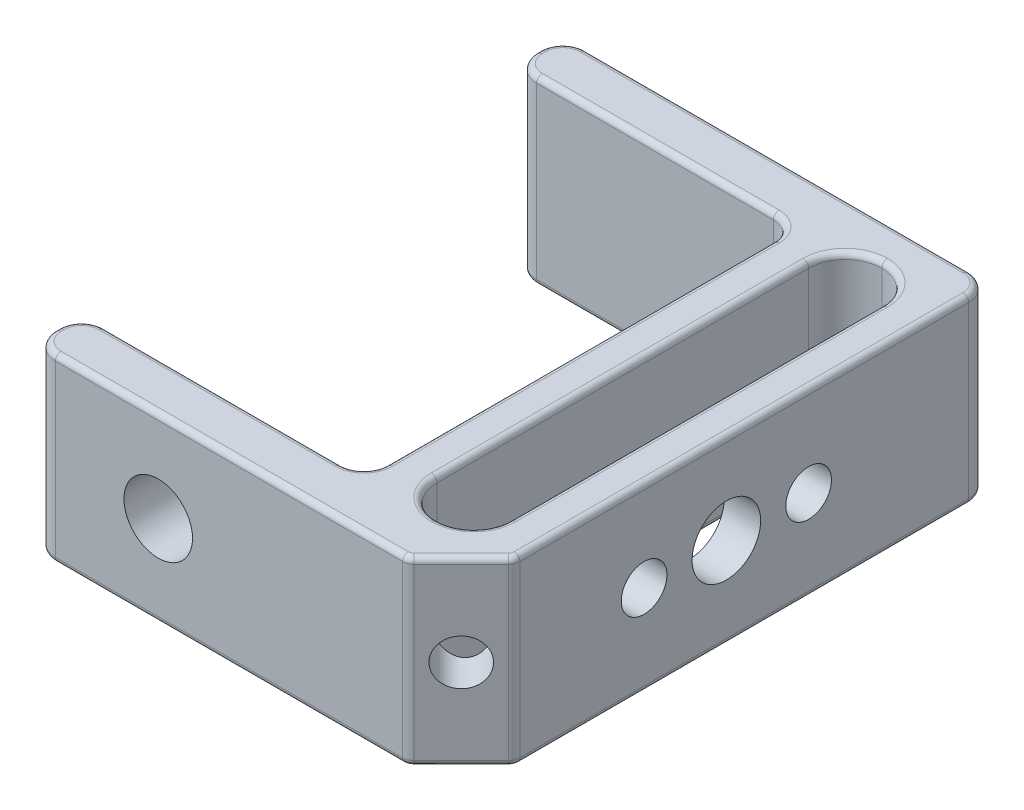
SolidWorks part; units mm, degrees
material "BUTYL"
ref_plane "Front Plane" through (0, 0, 0) normal (0, 0, 1) x (1, 0, 0)
ref_plane "Top Plane" through (0, 0, 0) normal (0, 1, 0) x (1, 0, 0)
ref_plane "Right Plane" through (0, 0, 0) normal (1, 0, 0) x (0, 0, -1)
sketch "Sketch1" plane through (0, 0, 0) normal (0, 1, 0) x (1, 0, 0)
  line L0 (0, 0) -> (0, -6.7945)
  line L1 (0, -6.7945) -> (39.243, -6.7945)
  line L2 (39.243, -6.7945) -> (39.243, -66.8655)
  line L3 (39.243, -66.8655) -> (0, -66.8655)
  line L4 (0, -66.8655) -> (0, -73.66)
  line L5 (0, 0) -> (59.563, 0)
  line L6 (59.563, 0) -> (59.563, -66.167)
  line L7 (59.563, -66.167) -> (52.07, -73.66)
  line L8 (52.07, -73.66) -> (0, -73.66)
  line L9 (44.323, -5.08) -> (54.483, -5.08)
  line L10 (54.483, -5.08) -> (54.483, -66.8655)
  line L11 (54.483, -66.8655) -> (44.323, -66.8655)
  line L12 (44.323, -66.8655) -> (44.323, -5.08)
  dimension "D1" = 6.7945
  dimension "D2" = 6.7945
  dimension "D3" = 10.16
  dimension "D4" = 59.563
  dimension "D5" = 60.071
  dimension "D6" = 5.08
  dimension "D7" = 5.08
  dimension "D8" = 5.08
  dimension "D9" = 135
  dimension "D10" = 52.07
extrude "Boss-Extrude1" add sketch "Sketch1" along normal blind 25.1841
fillet "Fillet2" radius 5.08 4 edges at (44.323, 12.5921, 5.08) (54.483, 12.5921, 5.08) (44.323, 12.5921, 66.8655) (54.483, 12.5921, 66.8655)
sketch "Sketch2" plane through (0, 0, 73.66) normal (0, 0, 1) x (1, 0, 0)
  line L0 (0, 12.5921) -> (17.4625, 12.5921) construction
  line L1 (0, 25.1841) -> (0, 0) construction
  circle A0 centre (17.4625, 12.5921) radius 4.7625
extrude "Cut-Extrude1" cut sketch "Sketch2" against normal up to next
sketch "Sketch3" plane through (62.865, 0, 62.865) normal (0.7071, 0, 0.7071) x (0.7071, 0, -0.7071)
  line L0 (-15.2664, 12.5921) -> (-4.6697, 12.5921) construction
  line L1 (-15.2664, 25.1841) -> (-15.2664, 0) construction
  line L2 (-4.6697, 25.1841) -> (-4.6697, 0) construction
  circle A0 centre (-9.9681, 12.5921) radius 3.175
extrude "Cut-Extrude2" cut sketch "Sketch3" against normal up to next
sketch "Sketch4" plane through (59.563, 0, 0) normal (1, 0, 0) x (0, 0, -1)
  line L0 (0, 12.5921) -> (-73.66, 12.5921)
  line L2 (-36.83, 12.5921) -> (-25.4, 12.592) construction
  line L3 (-36.83, 12.5921) -> (-48.26, 12.592) construction
  line L4 (0, 25.1841) -> (0, 0) construction
  line L5 (-73.66, 25.1841) -> (-73.66, 0) construction
  circle A0 centre (-36.83, 12.5921) radius 4.7625
  circle A1 centre (-25.4, 12.592) radius 3.175
  circle A2 centre (-48.26, 12.592) radius 3.175
  dimension "D2" = 11.43
  dimension "D3" = 11.43
extrude "Cut-Extrude3" cut sketch "Sketch4" against normal up to next contours L0 A0 | L0 A0 | L0 A1 | L0 A1 | L0 A2 | L0 A2 region at (59.563, 11.2445, 25.4) region at (59.563, 13.9396, 25.4) region at (59.563, 11.2445, 48.26) region at (59.563, 13.9396, 48.26) region at (59.563, 10.5708, 36.83) region at (59.563, 14.6133, 36.83)
sketch "Sketch6" plane through (0, 0, 0) normal (0, 0, -1) x (-1, 0, 0)
  line L0 (-59.563, 12.5921) -> (-49.53, 12.5921) construction
  line L1 (-59.563, 25.1841) -> (-59.563, 0) construction
  circle A0 centre (-49.53, 12.5921) radius 3.175
extrude "Cut-Extrude4" cut sketch "Sketch6" against normal up to next contours A0
fillet "Fillet3" radius 3.175 7 edges at (59.563, 12.5921, 0) (0, 12.5921, 73.66) (0, 12.5921, 66.8655) (39.243, 12.5921, 66.8655) (39.243, 12.5921, 6.7945) (0, 12.5921, 6.7945) (0, 12.5921, 0)
fillet "Fillet4" radius 1.5875 2 edges at (52.07, 12.5921, 73.66) (59.563, 12.5921, 66.167)
fillet "Fillet5" radius 0.7937 48 edges at (52.9951, 0, 65.3776) (45.8109, 0, 65.3776) (44.323, 0, 35.9728) (45.8109, 0, 6.5679) (52.9951, 0, 6.5679) (54.483, 0, 35.9728) (59.4422, 0, 66.1169) (59.563, 0, 34.3422) (58.6331, 0, 0.9299) (29.7815, 0, 0) (0.9299, 0, 0.9299) (0.9299, 0, 5.8646) (19.6215, 0, 6.7945) (38.3131, 0, 7.7244) (39.243, 0, 36.83) (38.3131, 0, 65.9356) (19.6215, 0, 66.8655) (0.9299, 0, 67.7954) (0.9299, 0, 72.7301) (27.2937, 0, 73.66) (52.0199, 0, 73.5392) (55.8165, 0, 69.9135) (44.323, 25.1841, 35.9728) (45.8109, 25.1841, 65.3776) (52.9951, 25.1841, 65.3776) (54.483, 25.1841, 35.9728) (52.9951, 25.1841, 6.5679) (45.8109, 25.1841, 6.5679) (0.9299, 25.1841, 72.7301) (0.9299, 25.1841, 67.7954) (19.6215, 25.1841, 66.8655) (38.3131, 25.1841, 65.9356) (39.243, 25.1841, 36.83) (38.3131, 25.1841, 7.7244) (19.6215, 25.1841, 6.7945) (0.9299, 25.1841, 5.8646) (0.9299, 25.1841, 0.9299) (29.7815, 25.1841, 0) (58.6331, 25.1841, 0.9299) (59.563, 25.1841, 34.3422) (59.4422, 25.1841, 66.1169) (55.8165, 25.1841, 69.9135) (52.0199, 25.1841, 73.5392) (27.2937, 25.1841, 73.66) (0, 0, 3.3973) (0, 0, 70.2628) (0, 25.1841, 70.2628) (0, 25.1841, 3.3973)
